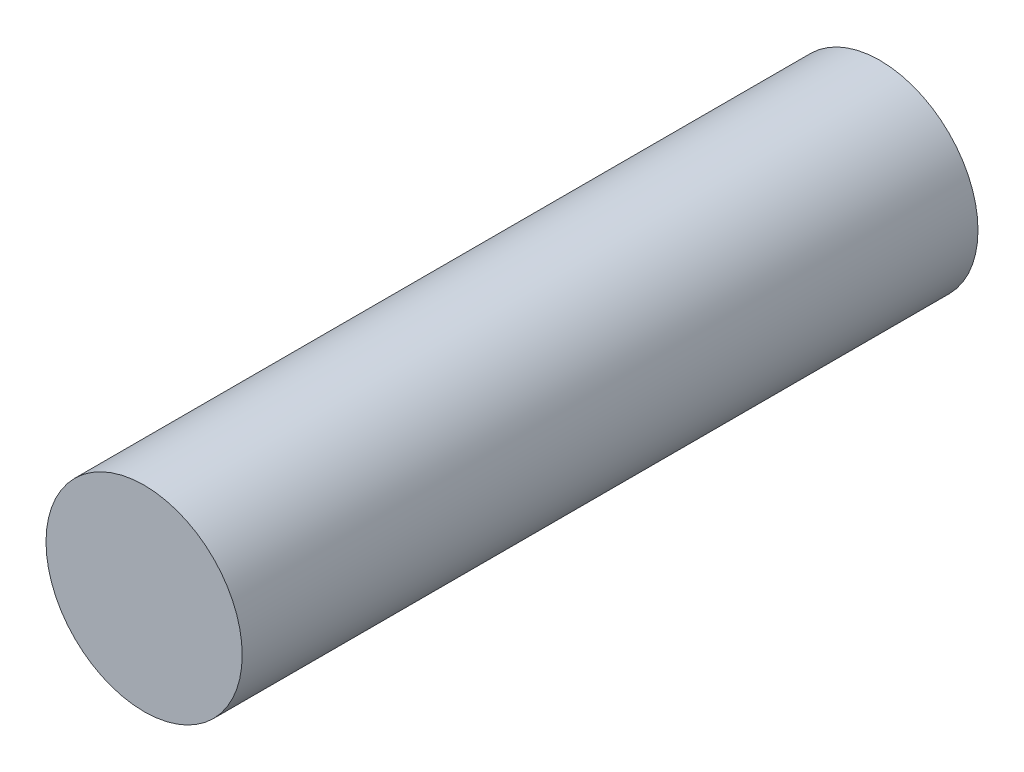
SolidWorks part; units mm, degrees
ref_plane "Front Plane" through (0, 0, 0) normal (0, 0, 1) x (1, 0, 0)
ref_plane "Top Plane" through (0, 0, 0) normal (0, 1, 0) x (1, 0, 0)
ref_plane "Right Plane" through (0, 0, 0) normal (1, 0, 0) x (0, 0, -1)
sketch "Sketch1" plane through (0, 0, 0) normal (0, 0, 1) x (1, 0, 0)
  circle A0 centre (0, 0) radius 12.7
  dimension "D1" = 25.4
extrude "Boss-Extrude1" add sketch "Sketch1" along normal blind 95.25
sketch "Sketch2" plane through (0, 0, 0) normal (0, 0, -1) x (-1, 0, 0)
  line L0 (0, 12.7) -> (0, -12.7) construction
  line L1 (6.35, 3.6662) -> (0, 7.3323)
  line L2 (0, 7.3323) -> (-6.35, 3.6662)
  line L3 (-6.35, 3.6662) -> (-6.35, -3.6662)
  line L4 (-6.35, -3.6662) -> (0, -7.3323)
  line L5 (0, -7.3323) -> (6.35, -3.6662)
  line L6 (6.35, -3.6662) -> (6.35, 3.6662)
  line L7 (-12.7, 0) -> (12.7, 0) construction
  circle A0 centre (0, 0) radius 6.35 construction
  circle A1 centre (0, 0) radius 12.7 construction
  point P15 (0, 0)
  point P16 (0, 0)
  point P17 (0, 0)
  dimension "D1" = 12.7
extrude "Cut-Extrude1" cut sketch "Sketch2" against normal blind 39.878
ref_axis "Axis1" through (0, 0, 95.25) along (0, 0, -1)
